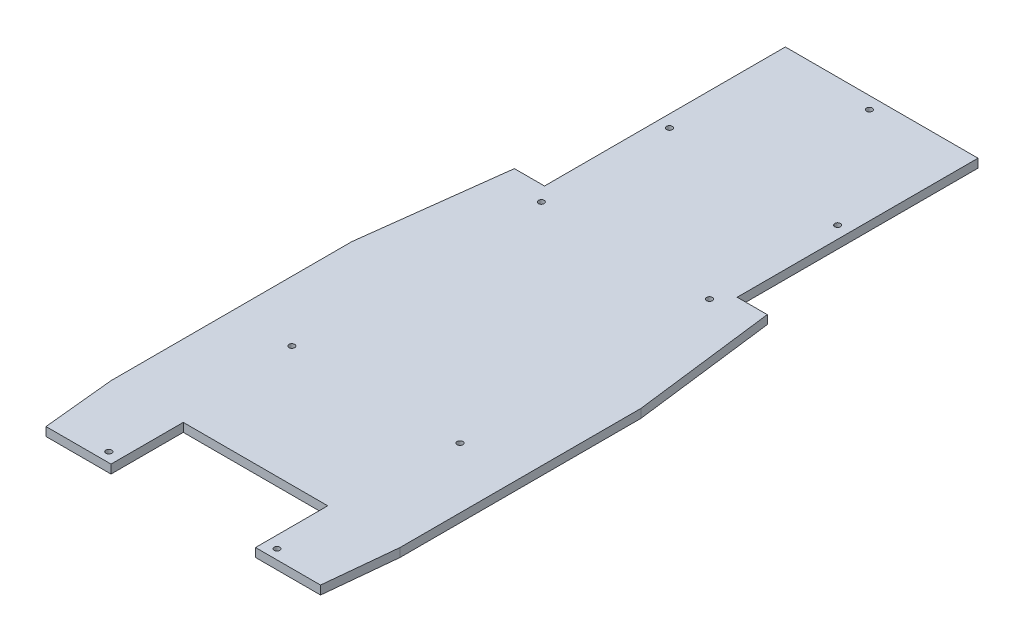
SolidWorks part; units mm, degrees
material "Pine"
ref_plane "Front Plane" through (0, 0, 0) normal (0, 0, 1) x (1, 0, 0)
ref_plane "Top Plane" through (0, 0, 0) normal (0, 1, 0) x (1, 0, 0)
ref_plane "Right Plane" through (0, 0, 0) normal (1, 0, 0) x (0, 0, -1)
sketch "Sketch1" plane through (0, 0, 0) normal (0, 1, 0) x (1, 0, 0)
  line L2 (-150, -125) -> (-150, 125)
  line L4 (150, -125) -> (150, 125)
  line L5 (-100, 525) -> (-150, 125)
  line L6 (-150, -125) -> (-125, -375)
  line L7 (-125, -375) -> (125, -375)
  line L16 (125, -375) -> (150, -125)
  line L17 (150, 125) -> (100, 525)
  line L18 (-100, 525) -> (100, 525)
  point P0 (0, 0)
  point P6 (0, 0)
  dimension "D1" = 300
  dimension "D2" = 250
  dimension "D3" = 125
  dimension "D4" = 200
  dimension "D5" = 125
  dimension "D6" = 100
  dimension "D7" = 900
  dimension "D8" = 400
extrude "Boss-Extrude1" add sketch "Sketch1" along normal blind 9
sketch "Sketch3" plane through (0, 9, 0) normal (0, 1, 0) x (1, 0, 0)
  line L0 (-125, -375) -> (125, -375) construction
  line L1 (-100, 525) -> (100, 525)
  line L2 (-100, 525) -> (-100, -375)
  line L3 (-100, -375) -> (100, -375)
  line L4 (100, 525) -> (100, -375)
  line L6 (0, 525) -> (0, -375) construction
  line L7 (-100, -375) -> (100, -375)
  line L8 (-100, -375) -> (-100, -299.5)
  line L9 (-100, -299.5) -> (100, -299.5)
  line L10 (100, -375) -> (100, -299.5)
  point P7 (0, 512.3)
  point P8 (-87.3, 392)
  point P9 (-87.3, 259)
  point P10 (-87.3, 0)
  point P11 (0, -286.8)
  point P14 (-87.3, -190)
  point P19 (87.3, -190)
  point P20 (87.3, 0)
  point P21 (87.3, 259)
  point P22 (87.3, 392)
  point P23 (0, 525)
  dimension "D1" = 200
  dimension "D2" = 12.7
  dimension "D3" = 12.7
  dimension "D4" = 133
  dimension "D5" = 133
  dimension "D6" = 125
  dimension "D7" = 65
  dimension "D8" = 75.5
  dimension "D9" = 12.7
hole_wizard "Ø6.0 (6) Diameter Hole1" positions "3DSketch3" profile "Sketch5" hole size "Ø6.0" standard "ANSI Metric" end condition through all
sketch3d "3DSketch3"
  point P0 (0, 9, -512.3)
  point P3 (-87.3, 9, -392)
  point P6 (-87.3, 9, -259)
  point P9 (87.3, 9, -259)
  point P12 (87.3, 9, -392)
  point P15 (87.3, 9, 0)
  point P18 (-87.3, 9, 0)
  point P21 (-87.3, 9, 190)
  point P24 (87.3, 9, 190)
  point P28 (0, 9, 286.8)
sketch "Sketch5" plane through (0, 9, -512.3) normal (1, 0, 0) x (0, 0, 1)
  line L0 (0, 0) -> (0, 9)
  line L1 (0, 9) -> (3, 9)
  line L2 (3, 9) -> (3, 0)
  line L5 (3, 0) -> (0, 0)
  line L11 (0, -6.35) -> (0, 107.95) construction
  dimension "Thru Hole Dia." = 6
  dimension "Thru Hole Depth" = 9
hole_wizard "Ø6.0 (6) Diameter Hole3" positions "3DSketch5" profile "Sketch7" hole size "Ø6.0" standard "ANSI Metric"
sketch3d "3DSketch5"
  line L0 (0, 0, -512.3) -> (0, 9, -512.3) construction
  line L1 (87.3, 0, -392) -> (87.3, 9, -392) construction
  line L2 (-87.3, 0, -392) -> (-87.3, 9, -392) construction
  line L3 (-87.3, 0, -259) -> (-87.3, 9, -259) construction
  line L4 (87.3, 0, -259) -> (87.3, 9, -259) construction
  line L5 (87.3, 0, 0) -> (87.3, 9, 0) construction
  line L6 (-87.3, 0, 0) -> (-87.3, 9, 0) construction
  line L7 (-87.3, 0, 190) -> (-87.3, 9, 190) construction
  line L8 (87.3, 0, 190) -> (87.3, 9, 190) construction
  line L9 (0, 0, 286.8) -> (0, 9, 286.8) construction
  point P0 (0, 0, -512.3)
  point P4 (87.3, 0, -392)
  point P8 (-87.3, 0, -392)
  point P12 (-87.3, 0, -259)
  point P16 (87.3, 0, -259)
  point P20 (87.3, 0, 0)
  point P24 (-87.3, 0, 0)
  point P28 (-87.3, 0, 190)
  point P32 (87.3, 0, 190)
  point P36 (0, 0, 286.8)
sketch "Sketch7" plane through (0, 0, -512.3) normal (1, 0, 0) x (0, 0, -1)
  line L0 (0, 0) -> (0, 36.3026)
  line L1 (0, 36.3026) -> (3, 34.5)
  line L2 (3, 34.5) -> (3, 0)
  line L5 (3, 0) -> (0, 0)
  line L10 (0, 36.3026) -> (-3, 34.5) construction
  line L11 (0, -6.35) -> (0, 107.95) construction
  dimension "Hole Dia." = 6
  dimension "Hole Depth" = 34.5
  dimension "Drill Angle" = 118
hole_wizard "Ø6.0 (6) Diameter Hole4" positions "Sketch9" profile "Sketch10" hole size "Ø6.0" standard "ANSI Metric" end condition through all
sketch "Sketch9" plane through (0, 9, 0) normal (0, 1, 0) x (1, 0, 0)
  point P0 (123, -311)
  point P3 (-123, -311)
sketch "Sketch10" plane through (123, 9, 311) normal (1, 0, 0) x (0, 0, 1)
  line L0 (0, 0) -> (0, 9)
  line L1 (0, 9) -> (6, 9)
  line L2 (3, 6) -> (3, 0)
  line L5 (3, 0) -> (0, 0)
  line L7 (6, 9) -> (3, 6)
  line L8 (-6, 9) -> (-3, 6) construction
  line L11 (0, -6.35) -> (0, 107.95) construction
  dimension "Thru Hole Dia." = 6
  dimension "Thru Hole Depth" = 9
  dimension "Far C'Sink Dia." = 12
  dimension "Far C'Sink Angle" = 90
hole_wizard "Ø6.0 (6) Diameter Hole5" positions "Sketch11" profile "Sketch12" hole size "Ø6.0" standard "ANSI Metric" end condition through all
sketch "Sketch11" plane through (0, 9, 0) normal (0, 1, 0) x (1, 0, 0)
  point P0 (-82, -363.75)
  point P3 (-82, -307.75)
  point P6 (82, -363.75)
  point P9 (82, -307.75)
sketch "Sketch12" plane through (-82, 9, 363.75) normal (1, 0, 0) x (0, 0, 1)
  line L0 (0, 0) -> (0, 9)
  line L1 (0, 9) -> (6, 9)
  line L2 (3, 6) -> (3, 0)
  line L5 (3, 0) -> (0, 0)
  line L7 (6, 9) -> (3, 6)
  line L8 (-6, 9) -> (-3, 6) construction
  line L11 (0, -6.35) -> (0, 107.95) construction
  dimension "Thru Hole Dia." = 6
  dimension "Thru Hole Depth" = 9
  dimension "Far C'Sink Dia." = 12
  dimension "Far C'Sink Angle" = 90
sketch "Sketch13" plane through (0, 9, 0) normal (0, 1, 0) x (1, 0, 0)
  line L0 (-125, -375) -> (125, -375)
  line L1 (125, -375) -> (142.5, -200)
  line L2 (125, -375) -> (150, -125) construction
  line L3 (142.5, -200) -> (75, -200)
  line L4 (75, -200) -> (75, -125)
  line L5 (75, -125) -> (-75, -125)
  line L6 (-75, -125) -> (-75, -200)
  line L7 (-75, -200) -> (-142.5, -200)
  line L8 (-150, -125) -> (-125, -375) construction
  line L9 (-142.5, -200) -> (-125, -375)
  line L10 (-100, 525) -> (-100, 275)
  line L11 (-100, 275) -> (-131.25, 275)
  line L12 (-100, 525) -> (-150, 125) construction
  line L13 (-131.25, 275) -> (-100, 525)
  line L14 (100, 525) -> (100, 275)
  line L15 (100, 275) -> (131.25, 275)
  line L16 (150, 125) -> (100, 525) construction
  line L17 (131.25, 275) -> (100, 525)
  dimension "D1" = 250
  dimension "D2" = 150
  dimension "D3" = 75
  dimension "D4" = 250
extrude "Cut-Extrude1" cut sketch "Sketch13" against normal through all
